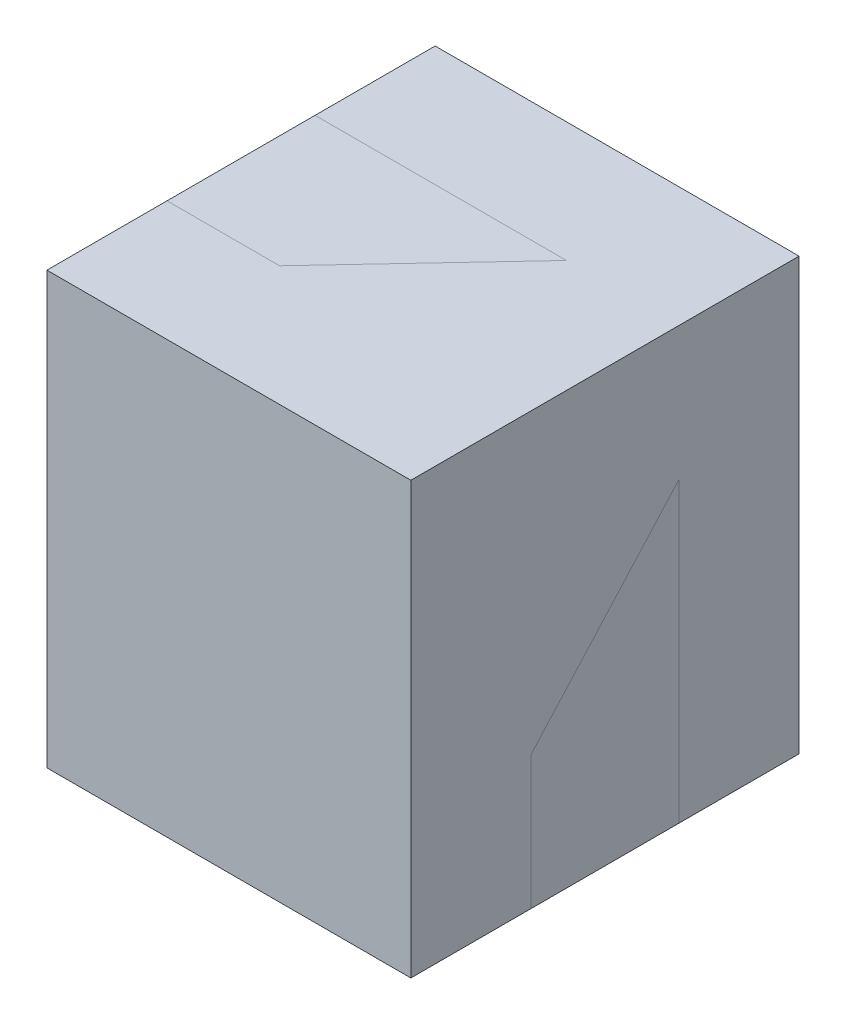
SolidWorks part; units mm, degrees
ref_plane "Front Plane" through (0, 0, 0) normal (0, 0, 1) x (1, 0, 0)
ref_plane "Top Plane" through (0, 0, 0) normal (0, 1, 0) x (1, 0, 0)
ref_plane "Right Plane" through (0, 0, 0) normal (1, 0, 0) x (0, 0, -1)
sketch "Sketch1" plane through (0, 0, 0) normal (0, 0, 1) x (1, 0, 0)
  line L1 (0, 0) -> (81.79, 0)
  line L2 (0, 0) -> (0, 96.88)
  line L3 (0, 96.88) -> (81.79, 96.88)
  line L4 (81.79, 0) -> (81.79, 96.88)
  dimension "D1" = 96.88
  dimension "D2" = 81.79
extrude "Boss-Extrude1" add sketch "Sketch1" along normal mid plane 33.27
sketch "Sketch2" plane through (0, 0, 16.635) normal (0, 0, 1) x (1, 0, 0)
  line L0 (0, 0) -> (81.79, 0) construction
  line L1 (19.735, 0) -> (62.055, 0)
  line L2 (14.735, 5) -> (14.735, 79.63)
  line L3 (19.735, 84.63) -> (62.055, 84.63)
  line L4 (67.055, 5) -> (67.055, 79.63)
  arc A0 (62.055, 0) -> (67.055, 5) centre (62.055, 5) ccw
  arc A1 (19.735, 0) -> (14.735, 5) centre (19.735, 5) cw
  arc A2 (62.055, 84.63) -> (67.055, 79.63) centre (62.055, 79.63) cw
  arc A3 (14.735, 79.63) -> (19.735, 84.63) centre (19.735, 79.63) cw
  point P7 (40.895, 0)
  point P8 (40.895, 0)
  point P13 (14.735, 0)
  point P16 (67.055, 84.63)
  point P19 (14.735, 84.63)
  dimension "D3" = 5
  dimension "D1" = 84.63
  dimension "D2" = 52.32
extrude "Boss-Extrude2" add sketch "Sketch2" along normal blind 26.99
fillet "Fillet1" radius 5 8 edges at (40.895, 0, 43.625) (16.1995, 1.4645, 43.625) (14.735, 42.315, 43.625) (16.1995, 83.1655, 43.625) (40.895, 84.63, 43.625) (65.5905, 83.1655, 43.625) (67.055, 42.315, 43.625) (65.5905, 1.4645, 43.625)
mirror "Mirror1" about plane through (0, 0, 0) normal (0, 0, 1) of "Boss-Extrude2", "Fillet1"
sketch "Sketch3" plane through (0, 0, 0) normal (0, -1, 0) x (1, 0, 0)
  line L0 (0, 0) -> (81.79, 0) construction
  line L1 (0, 16.635) -> (14.735, 16.635)
  line L2 (0, 16.635) -> (0, 37.16)
  line L3 (0, 37.16) -> (14.735, 37.16)
  line L4 (14.735, 16.635) -> (14.735, 37.16)
  line L5 (0, -16.635) -> (14.735, -16.635)
  line L6 (0, -16.635) -> (0, -37.16)
  line L7 (0, -37.16) -> (14.735, -37.16)
  line L8 (14.735, -16.635) -> (14.735, -37.16)
  line L9 (81.79, 16.635) -> (81.79, -16.635) construction
  line L10 (40.895, 0) -> (40.895, 43.625) construction
  line L11 (19.735, 43.625) -> (62.055, 43.625) construction
  line L12 (9.145, 27.955) -> (9.145, -27.955) construction
  line L13 (6.565, 30.535) -> (6.565, 25.375)
  line L14 (11.725, 25.375) -> (11.725, 30.535)
  line L15 (6.565, -30.535) -> (6.565, -25.375)
  line L16 (11.725, -25.375) -> (11.725, -30.535)
  line L17 (72.645, 27.955) -> (72.645, -27.955) construction
  line L18 (70.065, -25.375) -> (70.065, -30.535)
  line L19 (75.225, -30.535) -> (75.225, -25.375)
  line L20 (70.065, 25.375) -> (70.065, 30.535)
  line L21 (75.225, 30.535) -> (75.225, 25.375)
  line L22 (67.055, -16.635) -> (67.055, -37.16)
  line L23 (81.79, -37.16) -> (67.055, -37.16)
  line L24 (81.79, -16.635) -> (81.79, -37.16)
  line L25 (81.79, -16.635) -> (67.055, -16.635)
  line L26 (67.055, 16.635) -> (67.055, 37.16)
  line L27 (81.79, 37.16) -> (67.055, 37.16)
  line L28 (81.79, 16.635) -> (81.79, 37.16)
  line L29 (81.79, 16.635) -> (67.055, 16.635)
  arc A0 (6.565, 25.375) -> (11.725, 25.375) centre (9.145, 25.375) ccw
  arc A1 (11.725, 30.535) -> (6.565, 30.535) centre (9.145, 30.535) ccw
  arc A2 (6.565, 30.535) -> (9.145, 27.955) centre (9.145, 30.535) ccw construction
  arc A3 (9.145, 27.955) -> (6.565, 25.375) centre (9.145, 25.375) ccw construction
  arc A4 (11.725, 25.375) -> (9.145, 27.955) centre (9.145, 25.375) ccw construction
  arc A5 (9.145, 27.955) -> (11.725, 30.535) centre (9.145, 30.535) ccw construction
  arc A6 (6.565, -25.375) -> (11.725, -25.375) centre (9.145, -25.375) cw
  arc A7 (11.725, -30.535) -> (6.565, -30.535) centre (9.145, -30.535) cw
  arc A8 (72.645, 27.955) -> (70.065, 30.535) centre (72.645, 30.535) cw construction
  arc A9 (70.065, 25.375) -> (72.645, 27.955) centre (72.645, 25.375) cw construction
  arc A10 (72.645, 27.955) -> (75.225, 25.375) centre (72.645, 25.375) cw construction
  arc A11 (75.225, 30.535) -> (72.645, 27.955) centre (72.645, 30.535) cw construction
  arc A12 (70.065, -30.535) -> (75.225, -30.535) centre (72.645, -30.535) ccw
  arc A13 (75.225, -25.375) -> (70.065, -25.375) centre (72.645, -25.375) ccw
  arc A14 (70.065, 30.535) -> (75.225, 30.535) centre (72.645, 30.535) cw
  arc A15 (75.225, 25.375) -> (70.065, 25.375) centre (72.645, 25.375) cw
  point P22 (9.145, 0)
  dimension "D4" = 5.16
  dimension "D1" = 74.32
  dimension "D2" = 55.91
  dimension "D3" = 63.5
extrude "Boss-Extrude3" add sketch "Sketch3" against normal blind 1 separate body
fillet "Fillet2" radius 5 1 edges at (81.79, 0.5, 37.16)
fillet "Fillet3" radius 5 1 edges at (81.79, 0.5, -37.16)
fillet "Fillet4" radius 5 1 edges at (0, 0.5, 37.16)
fillet "Fillet5" radius 5 1 edges at (0, 0.5, -37.16)
sketch "Sketch4" plane through (0, 0, 0) normal (0, -1, 0) x (1, 0, 0)
  line L0 (19.735, 43.625) -> (62.055, 43.625) construction
  line L1 (0, 43.625) -> (81.79, 43.625)
  line L2 (0, 43.625) -> (0, -43.625)
  line L3 (0, -43.625) -> (81.79, -43.625)
  line L4 (81.79, 43.625) -> (81.79, -43.625)
  line L5 (0, 16.635) -> (0, -16.635) construction
  line L6 (81.79, 16.635) -> (81.79, -16.635) construction
  line L7 (62.055, -43.625) -> (19.735, -43.625) construction
extrude "Boss-Extrude4" add sketch "Sketch4" against normal up to surface (96.88 mm away) separate body up to face at (40.895, 96.88, 0)
sketch "Sketch5" plane through (0, 0, 0) normal (0, 1, 0) x (1, 0, 0)
  line L0 (-12.6198, 80.4108) -> (94.3802, 80.4108) construction
  dimension "D1" = 107
sketch "Sketch6" plane through (0, 0, 0) normal (0, -1, 0) x (1, 0, 0)
  line L0 (0, 0) -> (81.79, 0) construction
  line L1 (0, 16.635) -> (0, -16.635) construction
  line L2 (81.79, 16.635) -> (81.79, -16.635) construction
  line L3 (40.895, 28.525) -> (40.895, -28.525) construction
  circle A0 centre (40.895, 28.525) radius 6.35
  circle A1 centre (40.895, -28.525) radius 6.35
  point P8 (40.895, 0)
  point P9 (40.895, 0)
  dimension "D1" = 12.7
  dimension "D2" = 57.05
extrude "Boss-Extrude5" add sketch "Sketch6" along normal blind 2
ref_axis "Axis1" through (72.645, 1, -30.535) along (0, -1, 0)
ref_axis "Axis2" through (9.145, 1, 30.535) along (0, -1, 0)
